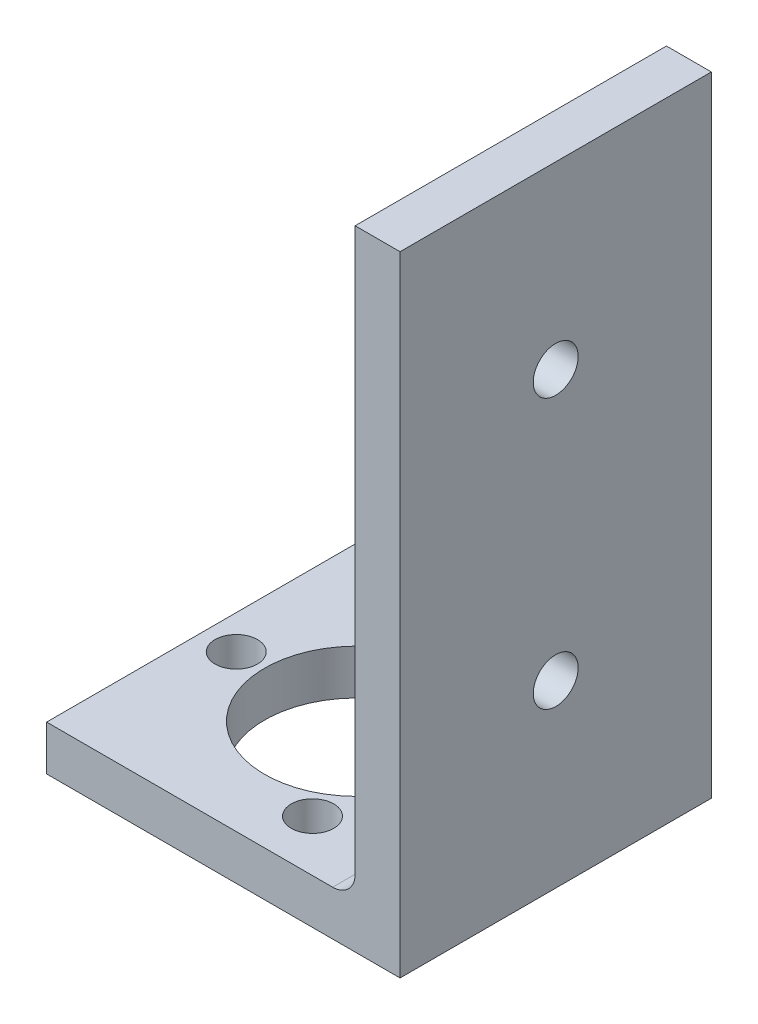
SolidWorks part; units mm, degrees
ref_plane "Front Plane" through (0, 0, 0) normal (0, 0, 1) x (1, 0, 0)
ref_plane "Top Plane" through (0, 0, 0) normal (0, 1, 0) x (1, 0, 0)
ref_plane "Right Plane" through (0, 0, 0) normal (1, 0, 0) x (0, 0, -1)
sketch "Sketch2" plane through (0, 0, 0) normal (0, 0, 1) x (1, 0, 0)
  line L0 (-25.4, 0) -> (25.4, 0)
  line L1 (25.4, 0) -> (25.4, 50.8)
  line L2 (25.4, 50.8) -> (22.225, 50.8)
  line L3 (22.225, 50.8) -> (22.225, 3.175)
  line L4 (22.225, 3.175) -> (-25.4, 3.175)
  line L5 (-25.4, 0) -> (-25.4, 3.175)
  line L6 (23.8125, 50.8) -> (25.4, 50.8) construction
  line L7 (-25.4, 1.5875) -> (-25.4, 0) construction
  dimension "Vert" = 50.8
  dimension "Horz" = 50.8
  dimension "Thickness" = 3.175
extrude "Boss-Extrude1" add sketch "Sketch2" along normal mid plane 22
fillet "Fillet1" radius 1.5875 1 edges at (22.225, 3.175, 0)
ref_plane "Contact Plane 1" through (0, 0, 0) normal (0, -1, 0) x (-1, 0, 0)
ref_plane "Contact Plane 2" through (25.4, 0, 0) normal (1, 0, 0) x (0, 0, -1)
ref_plane "Contact Plane 3" through (0, 3.175, 0) normal (0, 1, 0) x (1, 0, 0)
ref_plane "Contact Plane 4" through (22.225, 0, 0) normal (-1, 0, 0) x (0, 0, 1)
ref_plane "Contact Plane 5" through (0, 0, 11) normal (0, 0, 1) x (1, 0, 0)
ref_plane "Contact Plane 6" through (0, 0, -13.54) normal (0, 0, -1) x (-1, 0, 0)
sketch "Sketch3" plane through (0, 0, 11) normal (0, 0, 1) x (1, 0, 0)
  line L0 (-25.4, 0) -> (25.4, 0) construction
  line L1 (6.0591, 71.0024) -> (30.483, 71.0024)
  line L2 (6.0591, 71.0024) -> (6.0591, 44.45)
  line L3 (6.0591, 44.45) -> (30.483, 44.45)
  line L4 (30.483, 71.0024) -> (30.483, 44.45)
  dimension "D1" = 44.45
extrude "Cut-Extrude1" cut sketch "Sketch3" against normal through all
sketch "Sketch4" plane through (0, 0, 0) normal (0, -1, 0) x (1, 0, 0)
  line L0 (15.575, 7.3612) -> (15.575, -7.3612) construction
  line L1 (25.4, 11) -> (25.4, -11) construction
  line L2 (0.425, 11) -> (0.425, -11)
  line L3 (-25.4, 11) -> (25.4, 11) construction
  line L4 (-25.4, -11) -> (25.4, -11) construction
  circle A0 centre (11.325, 0) radius 6.5
  point P4 (15.575, 0)
  point P5 (25.4, 0)
  point P15 (11.325, 0)
  point P18 (11.325, 0)
  arc B0 (0.425, 0) -> (22.225, 0) centre (11.325, 0) ccw
  arc B1 (22.225, 0) -> (0.425, 0) centre (11.325, 0) ccw
  arc B2 (16.325, 8.6603) -> (14.825, 6.0622) centre (15.575, 7.3612) ccw
  arc B3 (14.825, 6.0622) -> (16.325, 8.6603) centre (15.575, 7.3612) ccw
  arc B4 (4.325, 0) -> (1.325, 0) centre (2.825, 0) ccw
  arc B5 (1.325, 0) -> (4.325, 0) centre (2.825, 0) ccw
  arc B6 (14.825, -6.0622) -> (16.325, -8.6603) centre (15.575, -7.3612) ccw
  arc B7 (16.325, -8.6603) -> (14.825, -6.0622) centre (15.575, -7.3612) ccw
  line M3 (-25.4, -11) -> (25.4, -11)
  line M5 (25.4, 11) -> (-25.4, 11)
  line M6 (-25.4, 11) -> (-25.4, -11)
  dimension "D1" = 13
sketch_block_instance "Block-MotorMounting-1"
sketch_block "Block-MotorMounting"
extrude "Cut-Extrude2" cut sketch "Sketch4" against normal through all contours L2 M5 M6 M3 | B4 B5 | B2 B3 | B6 B7 | L0 A0 | A0 L0 region at (16.9829, 0, -6.984) region at (16.4898, 0, 0) region at (10.6494, 0, 0) region at (15.1978, 0, 5.9533) region at (-12.4875, 0, 0) region at (2.825, 0, 0)
sketch "Sketch5" plane through (25.4, 0, 0) normal (1, 0, 0) x (0, 0, -1)
  line L0 (0, 44.45) -> (0, 31.75) construction
  line L1 (11, 44.45) -> (-11, 44.45) construction
  line L2 (0, 31.75) -> (0, 12.7) construction
  line L3 (0, 12.7) -> (0, 0) construction
  line L4 (-11, 0) -> (11, 0) construction
  circle A1 centre (0, 31.75) radius 1.5875
  circle A2 centre (0, 12.7) radius 1.5875
  dimension "D1" = 3.175
  dimension "D2" = 12.7
extrude "Cut-Extrude3" cut sketch "Sketch5" against normal through all
equation "\"D1@Fillet1\"=\"Thickness@Sketch2\"/2"
